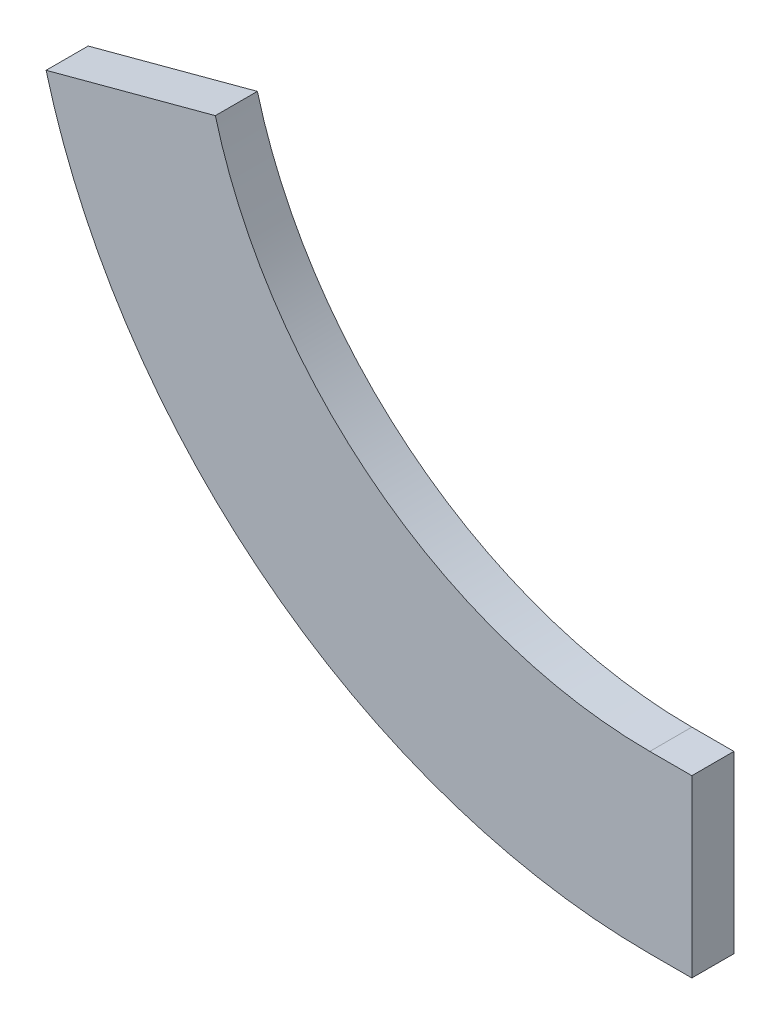
SolidWorks part; units mm, degrees
ref_plane "Front Plane" through (0, 0, 0) normal (0, 0, 1) x (1, 0, 0)
ref_plane "Top Plane" through (0, 0, 0) normal (0, 1, 0) x (1, 0, 0)
ref_plane "Right Plane" through (0, 0, 0) normal (1, 0, 0) x (0, 0, -1)
sketch "Sketch1" plane through (0, 0, 0) normal (0, 0, 1) x (1, 0, 0)
  line L0 (-79.4411, -31.75) -> (-82.4891, -31.75)
  line L1 (-113.979, -7.587) -> (-126.2462, -10.874)
  line L2 (-82.4891, -44.45) -> (-79.4411, -44.45)
  line L3 (-79.4411, -44.45) -> (-79.4411, -31.75)
  line L4 (-79.4411, -44.704) -> (-79.4411, -31.496) construction
  line L5 (-79.4411, -31.496) -> (-82.4891, -31.496) construction
  line L6 (-79.4411, -44.704) -> (-82.4891, -44.704) construction
  line L7 (-82.4891, -43.0472) -> (-82.4891, -2.54) construction
  line L8 (-82.4891, -43.0472) -> (-82.4891, -2.54) construction
  line L9 (-153.4846, -18.1724) -> (48142.8068, 12922.7798) construction
  arc A0 (-82.4891, -31.75) -> (-113.979, -7.587) centre (-82.4891, 0.8507) cw
  arc A1 (-126.2462, -10.874) -> (-82.4891, -44.45) centre (-82.4891, 0.8507) ccw
  dimension "D1" = 0.254
  dimension "D2" = 0.254
  dimension "D3" = 12.7
  dimension "D4" = 75
extrude "Boss-Extrude1" add sketch "Sketch1" along normal mid plane 3.048 contours A0 L1 A1 L2 L3 L0
